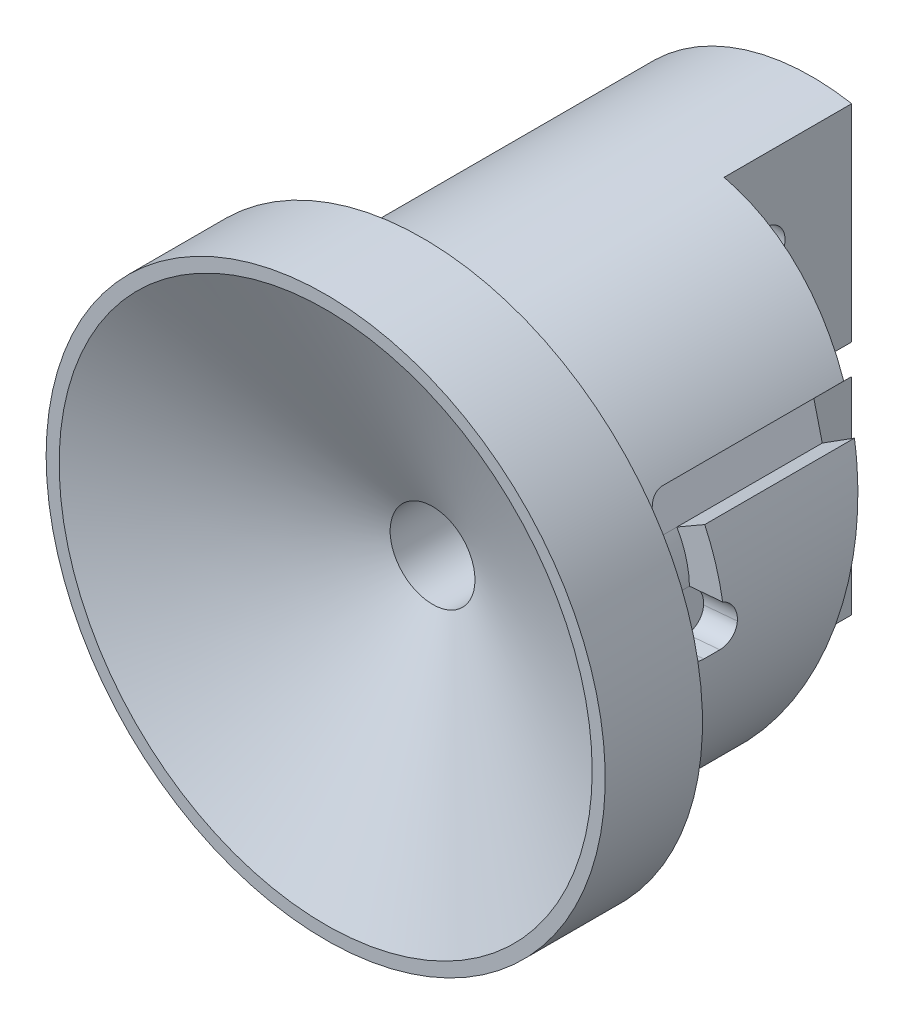
SolidWorks part; units mm, degrees
material "A-2 Steel"
ref_plane "Alzado" through (0, 0, 0) normal (0, 0, 1) x (1, 0, 0)
ref_plane "Planta" through (0, 0, 0) normal (0, 1, 0) x (1, 0, 0)
ref_plane "Vista lateral" through (0, 0, 0) normal (1, 0, 0) x (0, 0, -1)
sketch "Croquis2" plane through (0, 0, 0) normal (1, 0, 0) x (0, 0, -1)
  line L0 (0.3255, 0) -> (-7.0214, 0) construction
  line L1 (0, 2.7686) -> (31.75, 2.7686)
  line L2 (31.75, 2.7686) -> (31.75, 14.6812)
  line L3 (31.75, 14.6812) -> (6.35, 14.6812)
  line L4 (6.35, 14.6812) -> (6.35, 18.2499)
  line L5 (6.35, 18.2499) -> (0, 18.2499)
  line L6 (0, 18.2499) -> (0, 2.7686)
  dimension "D1" = 5.5372
  dimension "D2" = 36.4998
  dimension "D3" = 31.75
  dimension "D4" = 25.4
  dimension "D5" = 29.3624
revolve "Revolución1" add sketch "Croquis2" angle 360 about L0
sketch "Croquis3" plane through (0, 0, 0) normal (0, 1, 0) x (1, 0, 0)
  line L0 (0, 8.2982) -> (-17.399, 0)
  line L2 (-18.2499, 0) -> (18.2499, 0) construction
  line L3 (-17.399, 0) -> (0, 0)
  line L4 (0, 0) -> (0, 8.2982)
  line L5 (0, 0) -> (0, -3.613) construction
  dimension "D1" = 3.613
  dimension "D2" = 34.798
  dimension "D3" = 8.2982
revolve "Cortar-Revolución1" cut sketch "Croquis3" angle 360 about L5
sketch "Croquis4" plane through (0, 0, -31.75) normal (0, 0, -1) x (-1, 0, 0)
  line L0 (-2.5908, -14.4508) -> (-2.5908, 14.4508)
  circle A1 centre (0, 0) radius 14.6812 construction
  circle A3 centre (0, 0) radius 14.6812
  arc A4 (-2.5908, 14.4508) -> (-2.5908, -14.4508) centre (0, 0) ccw
  dimension "D1" = 2.5908
  dimension "D2" = 0
ref_plane "Plano1" through (2.5908, 0, 0) normal (-1, 0, 0) x (0, 1, 0)
sketch "Croquis5" plane through (2.5908, 0, 0) normal (-1, 0, 0) x (0, 1, 0)
  line L0 (14.4508, 23.4188) -> (-14.4508, 15.6746)
  line L1 (14.4508, 31.75) -> (-14.4508, 31.75) construction
  line L4 (-14.4508, 31.75) -> (-14.4508, 15.6746)
  line L6 (14.4508, 23.4188) -> (14.4508, 31.75)
  line L7 (-14.4508, 31.75) -> (14.4508, 31.75) construction
  line L8 (14.4508, 31.75) -> (-14.4508, 31.75)
  dimension "D1" = 15
  dimension "D2" = 8.3312
extrude "Cortar-Extruir1" cut sketch "Croquis5" against normal through all
hole_wizard "Taladro roscado #6-321" positions "Croquis6" profile "Croquis7" tap size "#6-32" standard "Ansi Inch"
sketch "Croquis6" plane through (2.5908, 0, 0) normal (1, 0, 0) x (0, 0, -1)
  line L0 (26.0446, 8.9408) -> (31.75, 8.9408) construction
  line L1 (31.75, -14.4508) -> (31.75, 14.4508) construction
  line L3 (0, 0) -> (31.75, 0) construction
  line L5 (19.8083, 0.9762) -> (23.4188, 14.4508) construction
  point P0 (26.0446, 8.9408)
  dimension "D1" = 8.9408
  dimension "D2" = 3.9624
sketch "Croquis7" plane through (2.5908, 8.9408, -26.0446) normal (0, 1, 0) x (0, 0, -1)
  line L0 (0, 0) -> (0, 11.7855)
  line L1 (0, 11.7855) -> (1.3525, 10.9728)
  line L2 (1.3525, 10.9728) -> (1.3525, 0)
  line L5 (1.3525, 0) -> (0, 0)
  line L10 (0, 11.7855) -> (-1.3526, 10.9728) construction
  line L11 (0, -6.35) -> (0, 107.95) construction
  dimension "Diámetro de perforador para roscar" = 2.7051
  dimension "Profundidad de perforador para roscar" = 10.9728
  dimension "Ángulo de perforador" = 118
cosmetic thread "Rosca de taladro1" parameters "D1"=7.0104, "D2"=3.5052
sketch "Croquis8" plane through (0, 0, -31.75) normal (0, 0, -1) x (-1, 0, 0)
  line L0 (-13.3178, 6.1786) -> (-11.4986, 5.1283)
  line L1 (-11.4986, 5.1283) -> (-10.1905, 7.3939)
  line L2 (-10.1905, 7.3939) -> (-12.0097, 8.4443)
  line L3 (0, 0) -> (-18.2499, 0) construction
  line L4 (0, 0) -> (-15.8049, 9.125) construction
  arc A0 (-2.5908, 14.4508) -> (-2.5908, -14.4508) centre (0, 0) ccw construction
  arc A1 (-12.0097, 8.4443) -> (-13.3178, 6.1786) centre (0, 0) ccw
  circle A2 centre (0, 0) radius 18.2499 construction
  point P12 (-10.8445, 6.2611)
  point P13 (-12.7143, 7.3406)
  dimension "D1" = 30
  dimension "D2" = 2.6162
  dimension "D3" = 2.159
extrude "Cortar-Extruir2" cut sketch "Croquis8" against normal offset from surface (22.9362 mm away) 2.4638 up to face at (-18.2499, 0, -6.35)
sketch "Croquis9" plane through (0, 0, -8.8138) normal (0, 0, -1) x (-1, 0, 0)
  line L0 (-10.8445, 6.2611) -> (0, 0) construction
  line L1 (-10.1905, 7.3939) -> (-11.4986, 5.1283) construction
  line L2 (0, 0) -> (-18.2499, 0) construction
  line L3 (0, 0) -> (-18.1805, 1.5906) construction
  line L5 (-12.3024, 2.3894) -> (-12.5304, -0.2168)
  line L6 (-12.5304, -0.2168) -> (-14.6812, -0.0287)
  line L7 (-11.0956, 5.8262) -> (-11.4986, 5.1283) construction
  line L8 (-11.0956, 5.8262) -> (-12.9579, 6.9014)
  circle A0 centre (0, 0) radius 18.2499 construction
  arc A1 (-13.3178, 6.1786) -> (-2.5908, -14.4508) centre (0, 0) ccw construction
  circle A2 centre (0, 0) radius 14.6812 construction
  arc A3 (-13.7662, 5.102) -> (-14.6812, -0.0287) centre (0, 0) ccw construction
  arc A4 (-11.0956, 5.8262) -> (-12.3024, 2.3894) centre (0, 0) ccw
  arc A5 (-12.9579, 6.9014) -> (-14.6812, -0.0287) centre (0, 0) ccw
  arc A6 (-12.0097, 8.4443) -> (-13.3178, 6.1786) centre (0, 0) ccw construction
  point P12 (-12.4164, 1.0863)
  point P15 (-14.4532, 2.5776)
  arc M11 (-12.0097, 8.4443) -> (-13.3178, 6.1786) centre (0, 0) ccw
  line M12 (-13.3178, 6.1786) -> (-11.4986, 5.1283)
  line M13 (-11.4986, 5.1283) -> (-10.1905, 7.3939)
  dimension "D1" = 25
  dimension "D2" = 2.6162
  dimension "D3" = 2.159
  dimension "D4" = 2.159
extrude "Cortar-Extruir3" cut sketch "Croquis9" along normal blind 2.6162 contours A5 L6 L5 A4 M12 M13 | L8 M13 M11 M12 region at (13.2214, 2.7992, -8.8138) region at (12.2183, 6.0109, -8.8138)
sketch "Croquis10" plane through (12.4164, 1.0863, 0) normal (0.9962, 0.0872, 0) x (0, 0, -1)
  line L0 (8.8138, 1.3081) -> (8.8138, -1.3081) construction
  line L1 (12.2428, -0.0974) -> (10.9347, -0.0974) construction
  line L3 (11.43, -1.3081) -> (11.43, 1.1133)
  arc A0 (11.43, -1.3081) -> (11.43, 1.1133) centre (10.9347, -0.0974) ccw
  dimension "D1" = 3.429
  dimension "D2" = 2.6162
extrude "Cortar-Extruir4" cut sketch "Croquis10" along normal through all
fillet "Redondeo1" radius 1.1938 2 edges at (11.1001, 7.9191, -8.8138) (13.6058, -0.1227, -8.8138)
sketch "Croquis11" plane through (0, 0, -11.43) normal (0, 0, 1) x (1, 0, 0)
  line L0 (10.1905, 7.3939) -> (11.4986, 5.1283) construction
  line L1 (11.0956, 5.8262) -> (11.4986, 5.1283)
  line L2 (12.5304, -0.2168) -> (12.3193, 2.1954) construction
  line L3 (12.3024, 2.3894) -> (12.3193, 2.1954)
  arc A0 (12.3193, 2.1954) -> (11.4986, 5.1283) centre (6.1834, 2.0595) ccw
  arc A10 (12.3024, 2.3894) -> (11.0956, 5.8262) centre (0, 0) ccw
  arc A11 (12.3024, 2.3894) -> (11.0956, 5.8262) centre (0, 0) ccw construction
extrude "Saliente-Extruir1" add sketch "Croquis11" along normal up to surface (2.6162 mm away) up to face at (12.3975, 4.0516, -8.8138)
fillet "Redondeo2" radius 1.1938 1 edges at (13.6058, -0.1227, -11.43)
